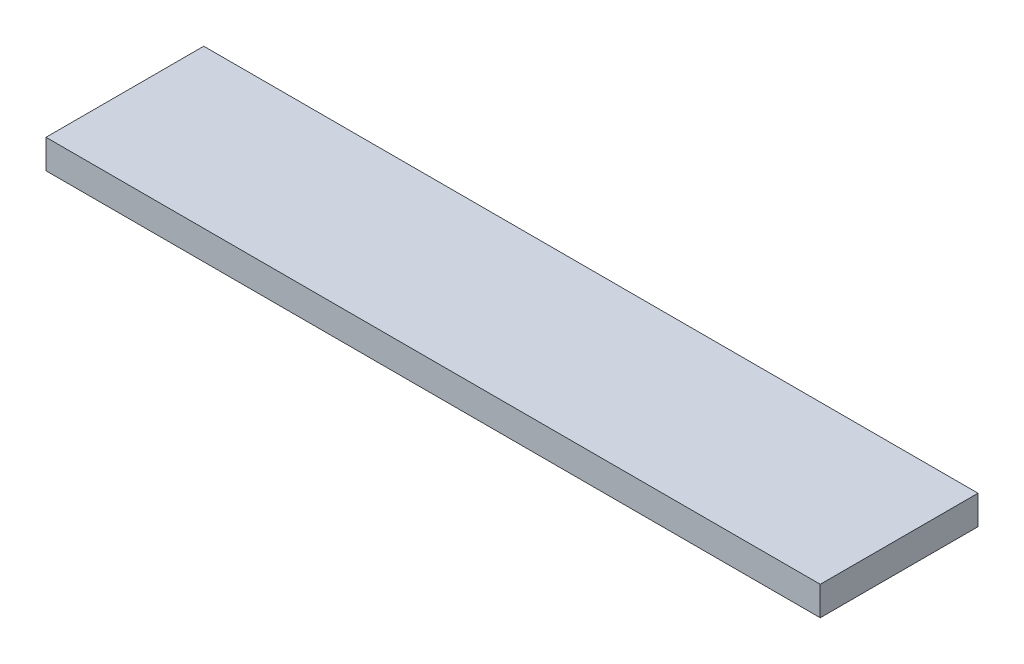
SolidWorks part; units mm, degrees
ref_plane "Front Plane" through (0, 0, 0) normal (0, 0, 1) x (1, 0, 0)
ref_plane "Top Plane" through (0, 0, 0) normal (0, 1, 0) x (1, 0, 0)
ref_plane "Right Plane" through (0, 0, 0) normal (1, 0, 0) x (0, 0, -1)
sketch "Sketch1" plane through (0, 0, 0) normal (0, 1, 0) x (1, 0, 0)
  line L0 (80, -80) -> (80, 0) construction
  line L1 (0, 0) -> (80, 0)
  line L2 (0, 0) -> (0, -16.3)
  line L3 (0, -16.3) -> (80, -16.3)
  line L4 (80, 0) -> (80, -16.3)
sketch "Sketch2" plane through (0, 0, 0) normal (1, 0, 0) x (0, 0, -1)
  line L1 (0, 0) -> (-16.3, 0)
  line L2 (0, 0) -> (0, -3)
  line L3 (0, -3) -> (-16.3, -3)
  line L4 (-16.3, 0) -> (-16.3, -3)
extrude "Boss-Extrude1" add sketch "Sketch1" against normal up to vertex (3 mm away) up to point (0, -3, 0)
